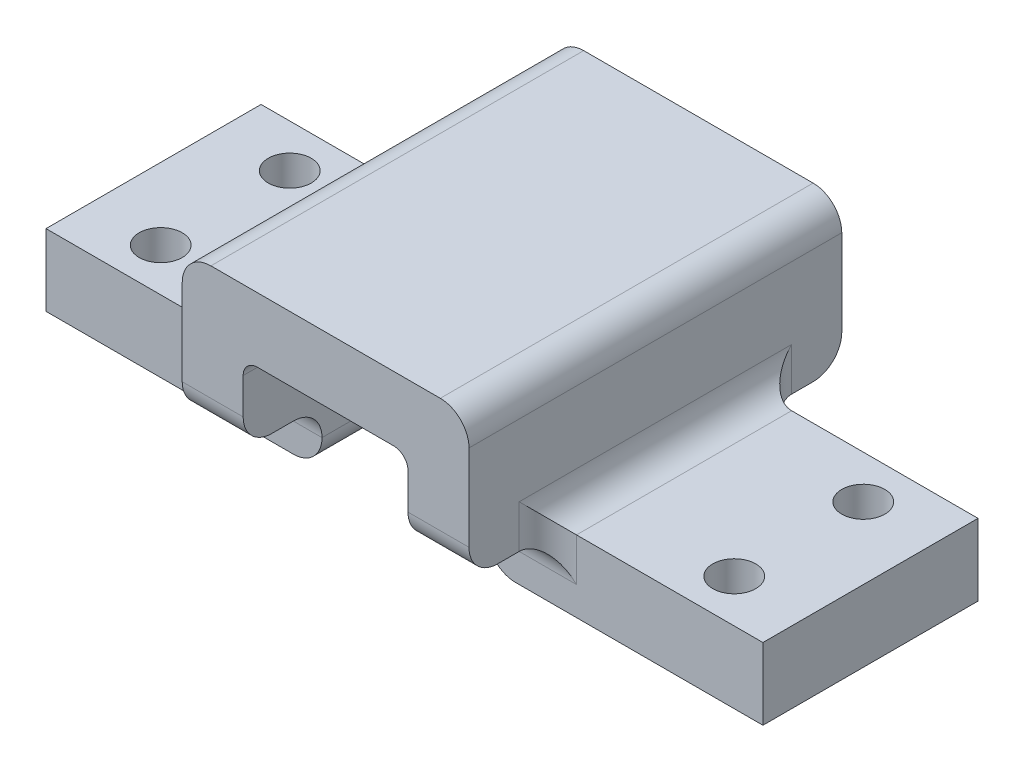
SolidWorks part; units mm, degrees
ref_plane "前基準面" through (0, 0, 0) normal (0, 0, 1) x (1, 0, 0)
ref_plane "上基準面" through (0, 0, 0) normal (0, 1, 0) x (1, 0, 0)
ref_plane "右基準面" through (0, 0, 0) normal (1, 0, 0) x (0, 0, -1)
sketch "草圖1" plane through (0, 0, 0) normal (0, 0, 1) x (1, 0, 0)
  line L0 (-11.5, -10) -> (-11.5, 1)
  line L1 (-20, -10) -> (-11.5, -10)
  line L2 (-20, -10) -> (-20, 10)
  line L3 (-20, 10) -> (20, 10)
  line L4 (20, -10) -> (20, 10)
  line L5 (-20, -10) -> (20, 10) construction
  line L6 (-20, 10) -> (20, -10) construction
  line L7 (-11.5, 1) -> (11.5, 1)
  line L8 (11.5, 1) -> (11.5, -10)
  line L9 (11.5, -10) -> (11.5, 1)
  line L10 (11.5, -10) -> (20, -10)
  line L11 (0, 0) -> (0, 51.1842) construction
  point P0 (0, 0)
  dimension "D1" = 40
  dimension "D2" = 23
  dimension "D3" = 20
  dimension "D4" = 11
extrude "填料-伸長1" add sketch "草圖1" along normal mid plane 52 contours L8 L10 L4 L3 L2 L1 L0 L7 region at (0, 2.0814, 0)
sketch "草圖2" plane through (0, -10, 0) normal (0, -1, 0) x (1, 0, 0)
  line L0 (0, 0) -> (31.5985, 0) construction
  line L1 (-50, -15) -> (-11.5, -15)
  line L2 (-50, -15) -> (-50, 15)
  line L3 (-50, 15) -> (-11.5, 15)
  line L5 (-50, -15) -> (0, 0) construction
  line L6 (-50, 15) -> (0, 0) construction
  line L7 (0, 0) -> (0, 29.2145) construction
  line L8 (50, -15) -> (50, 15)
  line L9 (-11.5, 15) -> (-11.5, -15)
  line L10 (50, 15) -> (11.5, 15)
  line L11 (11.5, 15) -> (11.5, -15)
  line L12 (50, -15) -> (11.5, -15)
  circle A0 centre (-40, 9) radius 3
  circle A3 centre (-40, -9) radius 3
  circle A4 centre (40, 9) radius 3
  circle A5 centre (40, -9) radius 3
  point P0 (0, 0)
  dimension "D2" = 6
  dimension "D1" = 30
  dimension "D3" = 6
  dimension "D4" = 10
  dimension "D5" = 50
extrude "填料-伸長2" add sketch "草圖2" along normal blind 8 and the other way blind 2
fillet "圓角1" radius 4 14 edges at (20, 10, 0) (-20, 10, 0) (-11.5, -18, 0) (-20, -8, 0) (-15.75, -10, -15) (15.75, -10, -15) (-15.75, -10, 15) (15.75, -10, 15) (20, -8, 0) (11.5, -18, 0) (-20, -9, 15) (-20, -9, -15) (20, -9, -15) (20, -9, 15)
fillet "圓角2" radius 4 4 edges at (15.75, -10, -26) (-15.75, -10, -26) (-15.75, -10, 26) (15.75, -10, 26)
fillet "圓角3" radius 2 2 edges at (11.5, 1, 0) (-11.5, 1, 0)
